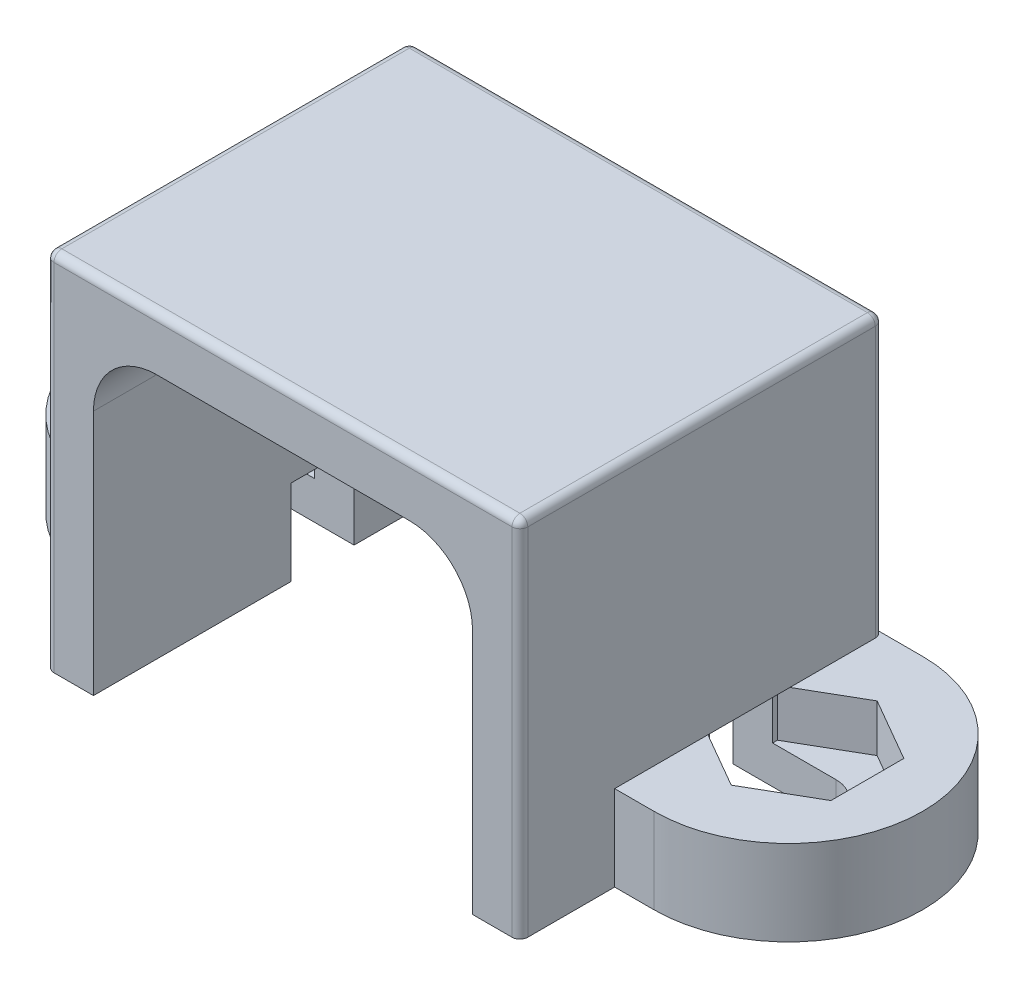
SolidWorks part; units mm, degrees
material "ABS"
ref_plane "Přední rovina" through (0, 0, 0) normal (0, 0, 1) x (1, 0, 0)
ref_plane "Horní rovina" through (0, 0, 0) normal (0, 1, 0) x (1, 0, 0)
ref_plane "Pravá rovina" through (0, 0, 0) normal (1, 0, 0) x (0, 0, -1)
sketch "Skica1" plane through (0, 0, 0) normal (0, 0, 1) x (1, 0, 0)
  line L0 (-13, 0) -> (-6, 0)
  line L1 (-6, 0) -> (-6, 7.798)
  line L2 (-4, 9.798) -> (4, 9.798)
  line L3 (-13, 0) -> (-13, 2.7)
  line L4 (-13, 2.7) -> (-7.5, 2.7)
  line L5 (-7.5, 2.7) -> (-7.5, 11.5)
  line L6 (-7.5, 11.5) -> (7.5, 11.5)
  line L7 (0, 0) -> (0, 11.5) construction
  line L8 (7.5, 2.7) -> (7.5, 11.5)
  line L9 (13, 2.7) -> (7.5, 2.7)
  line L10 (13, 0) -> (13, 2.7)
  line L11 (6, 0) -> (6, 7.798)
  line L12 (13, 0) -> (6, 0)
  arc A0 (-6, 7.798) -> (-4, 9.798) centre (-4, 7.798) cw
  arc A1 (4, 9.798) -> (6, 7.798) centre (4, 7.798) cw
  point P15 (0, 9.798)
  dimension "D7" = 2
  dimension "D1" = 12
  dimension "D2" = 10
  dimension "D3" = 11.5
  dimension "D4" = 15
  dimension "D5" = 26
  dimension "D6" = 2.7
extrude "Přidat vysunutím1" add sketch "Skica1" along normal blind 11.5
sketch "Skica3" plane through (0, 2.7, 0) normal (0, 1, 0) x (1, 0, 0)
  line L0 (-7.5, 0) -> (-13, 0) construction
  line L1 (-13, -11.5) -> (-13, 0) construction
  line L2 (-8.75, 0) -> (-7.5, 0)
  line L3 (-7.5, 0) -> (7.5, 0)
  line L4 (7.5, 0) -> (-7.5, 0) construction
  line L5 (0, 0) -> (0, -11.5) construction
  line L6 (7.5, -11.5) -> (-7.5, -11.5) construction
  line L7 (-8.75, -8.5) -> (-7.5, -8.5)
  line L8 (-7.5, -11.5) -> (-7.5, 0) construction
  line L9 (-7.5, -8.5) -> (-7.5, -11.5)
  line L10 (-7.5, -11.5) -> (7.5, -11.5)
  line L11 (7.5, -8.5) -> (7.5, -11.5)
  line L12 (8.75, -8.5) -> (7.5, -8.5)
  line L13 (8.75, 0) -> (7.5, 0)
  arc A0 (-8.75, 0) -> (-8.75, -8.5) centre (-8.75, -4.25) ccw
  arc A1 (8.75, 0) -> (8.75, -8.5) centre (8.75, -4.25) cw
  dimension "D1" = 8.5
extrude "Odebrat vysunutím1" cut sketch "Skica3" against normal through all flip side to cut
sketch "Skica4" plane through (0, 2.7, 0) normal (0, 1, 0) x (1, 0, 0)
  line L0 (0, 0) -> (0, -11.5) construction
  line L1 (7.5, -11.5) -> (-7.5, -11.5) construction
  line L2 (-6, -11.5) -> (-6, 0) construction
  line L3 (9.25, -5.25) -> (6, -5.25)
  line L4 (-9.25, -4.25) -> (-4.4647, -4.25) construction
  line L5 (-7.5, 0) -> (-8.75, 0) construction
  line L6 (-8.75, -8.5) -> (-7.5, -8.5) construction
  line L8 (9.25, -3.25) -> (6, -3.25)
  line L9 (6, -5.25) -> (6, -3.25)
  line L10 (-9.25, -5.25) -> (-6, -5.25)
  line L12 (-9.25, -3.25) -> (-6, -3.25)
  line L13 (-6, -5.25) -> (-6, -3.25)
  arc A0 (-9.25, -3.25) -> (-9.25, -5.25) centre (-9.25, -4.25) ccw
  arc A1 (-8.75, 0) -> (-8.75, -8.5) centre (-8.75, -4.25) ccw construction
  arc A2 (9.25, -3.25) -> (9.25, -5.25) centre (9.25, -4.25) cw
  point P22 (-13, -4.25)
  dimension "D1" = 2.75
  dimension "D2" = 2
extrude "Odebrat vysunutím2" cut sketch "Skica4" against normal through all
sketch "Skica5" plane through (0, 2.7, 0) normal (0, 1, 0) x (1, 0, 0)
  line L0 (0, 0) -> (0, -11.5) construction
  line L1 (-7.25, -5.4047) -> (-7.25, -3.0953)
  line L2 (-7.25, -3.0953) -> (-9.25, -1.9406)
  line L3 (-9.25, -1.9406) -> (-11.25, -3.0953)
  line L4 (-11.25, -3.0953) -> (-11.25, -5.4047)
  line L5 (-11.25, -5.4047) -> (-9.25, -6.5594)
  line L6 (-9.25, -6.5594) -> (-7.25, -5.4047)
  line L7 (7.5, -11.5) -> (-7.5, -11.5) construction
  line L8 (9.25, -6.5594) -> (7.25, -5.4047)
  line L9 (11.25, -5.4047) -> (9.25, -6.5594)
  line L10 (11.25, -3.0953) -> (11.25, -5.4047)
  line L11 (9.25, -1.9406) -> (11.25, -3.0953)
  line L12 (7.25, -3.0953) -> (9.25, -1.9406)
  line L13 (7.25, -5.4047) -> (7.25, -3.0953)
  circle A0 centre (-9.25, -4.25) radius 2 construction
  circle A1 centre (9.25, -4.25) radius 2 construction
  dimension "D1" = 4
extrude "Odebrat vysunutím3" cut sketch "Skica5" against normal blind 1.5
sketch "Skica6" plane through (0, 0, 0) normal (0, -1, 0) x (1, 0, 0)
  line L0 (-6, 11.5) -> (-6, 5.25) construction
  line L1 (-6, 9.3) -> (6, 9.3)
  line L2 (-6, 9.3) -> (-6, 8)
  line L3 (-6, 8) -> (6, 8)
  line L4 (6, 9.3) -> (6, 8)
  line L5 (6, 11.5) -> (6, 0) construction
  line L6 (-4, 11.5) -> (4, 11.5) construction
  line L7 (-4, 0) -> (4, 0) construction
  dimension "D1" = 2.2
  dimension "D2" = 8
extrude "Odebrat vysunutím4" cut sketch "Skica6" against normal up to surface (9.798 mm away) up to face at (0, 9.798, 5.75)
fillet "Zaoblit2" radius 0.25 12 edges at (7.5, 5.75, 11.5) (0, 11.5, 11.5) (-7.5, 5.75, 11.5) (-7.5, 7.1, 0) (-7.5, 11.5, 5.75) (7.5, 7.1, 0) (0, 11.5, 0) (7.5, 11.5, 5.75) (5.4142, 9.2122, 8) (5.4142, 9.2122, 9.3) (-5.4142, 9.2122, 8) (-5.4142, 9.2122, 9.3) tangent propagation no
